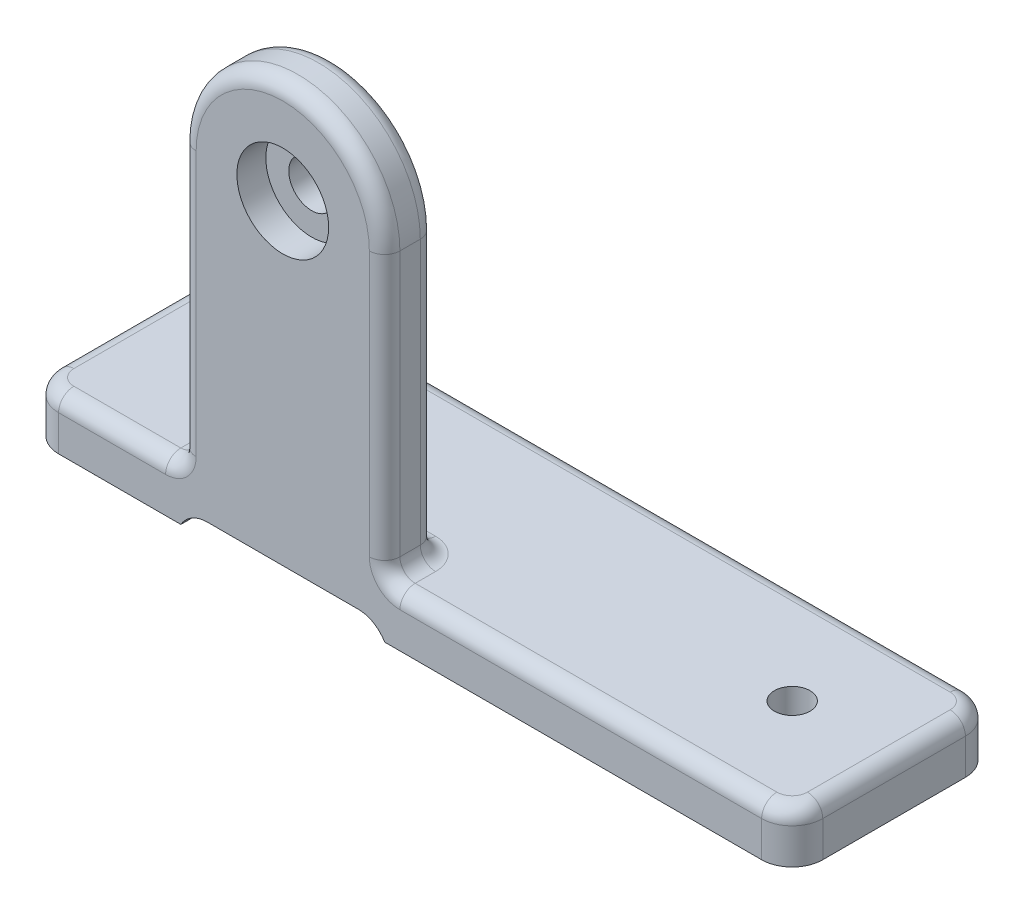
SolidWorks part; units mm, degrees
ref_plane "Front Plane" through (0, 0, 0) normal (0, 0, 1) x (1, 0, 0)
ref_plane "Top Plane" through (0, 0, 0) normal (0, 1, 0) x (1, 0, 0)
ref_plane "Right Plane" through (0, 0, 0) normal (1, 0, 0) x (0, 0, -1)
sketch "Sketch1" plane through (0, 0, 0) normal (0, 1, 0) x (1, 0, 0)
  line L1 (0, 0) -> (150, 0)
  line L2 (0, 0) -> (0, 40)
  line L3 (0, 40) -> (150, 40)
  line L4 (150, 0) -> (150, 40)
  dimension "D1" = 150
  dimension "D2" = 40
extrude "Base Plate" add sketch "Sketch1" along normal blind 10
sketch "Sketch2" plane through (0, 0, 0) normal (0, 0, 1) x (1, 0, 0)
  line L0 (30, 0) -> (30, 65)
  line L1 (0, 0) -> (150, 0) construction
  line L2 (70, 65) -> (70, 0)
  line L3 (70, 0) -> (30, 0)
  line L4 (0, 10) -> (0, 0) construction
  arc A0 (30, 65) -> (70, 65) centre (50, 65) cw
  dimension "D1" = 20
  dimension "D2" = 50
  dimension "D3" = 65
extrude "Vert Boss" add sketch "Sketch2" against normal blind 10
sketch "Sketch5" plane through (0, 0, 0) normal (0, 0, 1) x (1, 0, 0)
  line L0 (0, 0) -> (150, 0) construction
  line L1 (30, 0) -> (70, 0)
  line L2 (30, 0) -> (30, 3)
  line L3 (30, 3) -> (70, 3)
  line L4 (70, 0) -> (70, 3)
  line L5 (30, 65) -> (30, 10) construction
  line L6 (70, 10) -> (70, 65) construction
  dimension "D1" = 3
extrude "Slot" cut sketch "Sketch5" against normal through all
hole_wizard "Ø7.0 (7) Diameter Hole1" positions "Sketch9" profile "Sketch8" hole size "Ø7.0" standard "Ansi Metric" end condition through all
sketch "Sketch9" plane through (0, 10, 0) normal (0, 1, 0) x (-1, 0, 0)
  line L0 (-150, 0) -> (-150, -40) construction
  line L1 (-150, -40) -> (0, -40) construction
  line L2 (0, -40) -> (0, 0) construction
  point P0 (-130, -20)
  point P1 (-20, -20)
  dimension "D1" = 20
  dimension "D2" = 20
  dimension "D3" = 20
sketch "Sketch8" plane through (130, 10, -20) normal (1, 0, 0) x (0, 0, 1)
  line L0 (0, 0) -> (0, 10)
  line L1 (0, 10) -> (3.5, 10)
  line L2 (3.5, 10) -> (3.5, 0)
  line L5 (3.5, 0) -> (0, 0)
  line L11 (0, -6.35) -> (0, 107.95) construction
  dimension "Thru Hole Dia." = 7
  dimension "Thru Hole Depth" = 10
hole_wizard "CBORE for M8 Hex Head Bolt1" positions "Sketch4" profile "Sketch3" counterbore size "M8" standard "Ansi Metric" end condition through all
sketch "Sketch4" plane through (0, 0, 0) normal (0, 0, 1) x (1, 0, 0)
  point P0 (50, 65)
sketch "Sketch3" plane through (50, 65, 0) normal (1, 0, 0) x (0, -1, 0)
  line L0 (0, 0) -> (0, 40)
  line L1 (0, 40) -> (4.5, 40)
  line L3 (4.5, 40) -> (4.5, 5.68)
  line L4 (4.5, 5.68) -> (9.005, 5.68)
  line L5 (9.005, 5.68) -> (9.005, 0)
  line L7 (9.005, 0) -> (0, 0)
  line L11 (0, -6.35) -> (0, 107.95) construction
  dimension "Thru Hole Dia." = 9
  dimension "Thru Hole Depth" = 40
  dimension "C'Bore Dia." = 18.01
  dimension "C'Bore Depth" = 5.68
fillet "Fillet1" radius 6 6 edges at (70, 3, -20) (30, 3, -20) (0, 5, 0) (0, 5, -40) (150, 5, -40) (150, 5, 0)
fillet "Fillet2" radius 3 18 edges at (1.7574, 10, -38.2426) (0, 10, -20) (75, 10, -40) (1.7574, 10, -1.7574) (148.2426, 10, -38.2426) (18, 10, 0) (150, 10, -20) (30, 10, -5) (148.2426, 10, -1.7574) (50, 10, -10) (107, 10, 0) (70, 37.5, -10) (30, 37.5, -10) (70, 37.5, 0) (30, 37.5, 0) (70, 10, -5) (50, 85, -10) (50, 85, 0)
